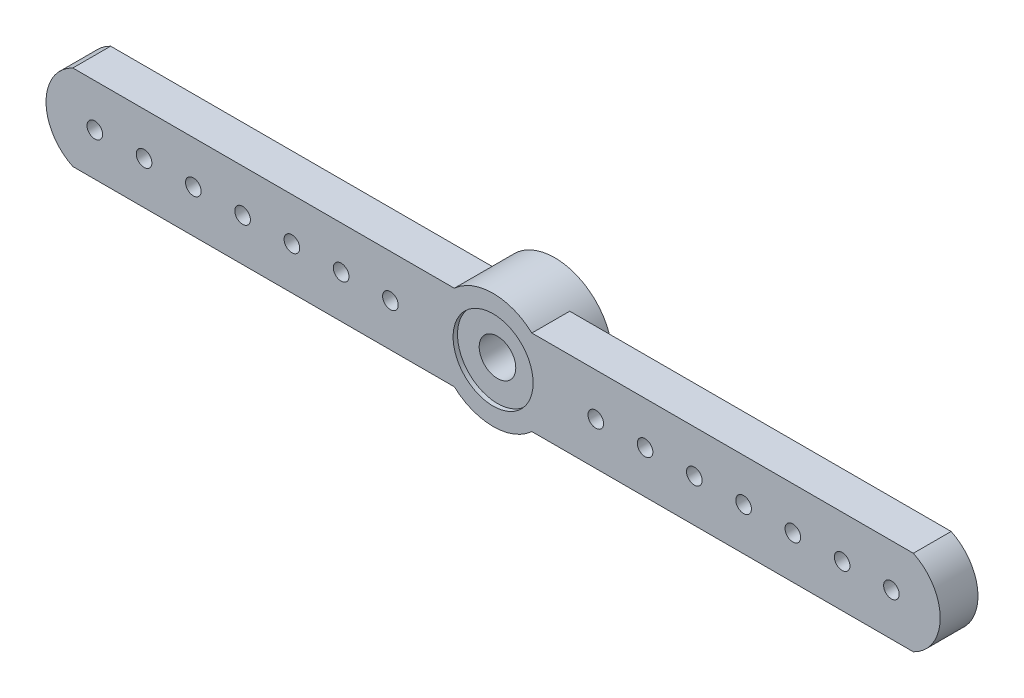
SolidWorks part; units mm, degrees
material "ABS"
ref_plane "Front Plane" through (0, 0, 0) normal (0, 0, 1) x (1, 0, 0)
ref_plane "Top Plane" through (0, 0, 0) normal (0, 1, 0) x (1, 0, 0)
ref_plane "Right Plane" through (0, 0, 0) normal (1, 0, 0) x (0, 0, -1)
sketch "Sketch1" plane through (0, 0, 0) normal (0, 0, 1) x (1, 0, 0)
  line L0 (-23.2791, 0) -> (23.2791, 0) construction
  line L1 (-23.2791, 2.2225) -> (23.2791, 2.2225)
  line L2 (-23.2791, 2.2225) -> (-23.2791, -2.2225)
  line L3 (-23.2791, -2.2225) -> (23.2791, -2.2225)
  line L4 (23.2791, 2.2225) -> (23.2791, -2.2225)
  line L5 (0, 0) -> (0, 17.0411) construction
  circle A0 centre (0, 0) radius 3.0035
  arc A1 (-21.8821, 2.2225) -> (-21.8821, -2.2225) centre (-20.8127, 0) ccw
  arc A2 (21.8821, 2.2225) -> (21.8821, -2.2225) centre (20.8127, 0) cw
  dimension "D3" = 6.0071
  dimension "D1" = 4.445
  dimension "D2" = 46.5582
  dimension "D4" = 1.397
extrude "Boss-Extrude1" add sketch "Sketch1" along normal blind 1.9685 contours L3 A0 | L1 A0 L3 | L1 A0 | A2 L1 A0 L3 | L1 A1 L3 A0 region at (-12.7938, 0, 0) region at (0, 2.5387, 0) region at (0, 0, 0) region at (12.7938, 0, 0) region at (0, -2.5387, 0)
sketch "Sketch2" plane through (0, 0, 1.9685) normal (0, 0, 1) x (1, 0, 0)
  line L0 (0, 0) -> (0, 12.9288) construction
  line L1 (-21.1455, 0) -> (-21.1455, 5.6069) construction
  line L2 (-20.3327, 0) -> (-20.3327, 7.4638) construction
  line L4 (-5.7531, 0) -> (-5.7531, 5.7068) construction
  circle A0 centre (-20.7391, 0) radius 0.4064
  arc A1 (21.8821, -2.2225) -> (21.8821, 2.2225) centre (20.8127, 0) ccw construction
  arc A2 (-21.8821, 2.2225) -> (-21.8821, -2.2225) centre (-20.8127, 0) ccw construction
  circle A3 centre (-18.1737, 0) radius 0.4064
  circle A4 centre (-15.6083, 0) radius 0.4064
  circle A5 centre (-13.0429, 0) radius 0.4064
  circle A6 centre (-10.4775, 0) radius 0.4064
  circle A7 centre (-7.9121, 0) radius 0.4064
  circle A8 centre (-5.3467, 0) radius 0.4064
  circle A9 centre (5.3467, 0) radius 0.4064
  circle A10 centre (7.9121, 0) radius 0.4064
  circle A11 centre (10.4775, 0) radius 0.4064
  circle A12 centre (13.0429, 0) radius 0.4064
  circle A13 centre (15.6083, 0) radius 0.4064
  circle A14 centre (18.1737, 0) radius 0.4064
  circle A15 centre (20.7391, 0) radius 0.4064
  point P11 (-23.2791, 0)
  dimension "D1" = 0.8128
  dimension "D2" = 2.1336
  dimension "D4" = 14.5796
  dimension "D3" = 7
extrude "Cut-Extrude1" cut sketch "Sketch2" against normal through all
sketch "Sketch3" plane through (0, 0, 1.9685) normal (0, 0, 1) x (1, 0, 0)
  circle A0 centre (0, 0) radius 2.0828
  dimension "D1" = 4.1656
extrude "Cut-Extrude2" cut sketch "Sketch3" against normal blind 0.2286
sketch "Sketch4" plane through (0, 0, 1.7399) normal (0, 0, 1) x (1, 0, 0)
  circle A0 centre (0, 0) radius 0.9525
  dimension "D1" = 1.905
extrude "Cut-Extrude3" cut sketch "Sketch4" against normal through all
sketch "Sketch5" plane through (0, 0, 0) normal (0, 0, -1) x (-1, 0, 0)
  circle A0 centre (0, 0) radius 3.0035
  circle A1 centre (0, 0) radius 1.7335
  arc A3 (-2.0203, -2.2225) -> (2.0203, -2.2225) centre (0, 0) ccw construction
  dimension "D1" = 1.27
extrude "Boss-Extrude2" add sketch "Sketch5" along normal blind 1.2446
